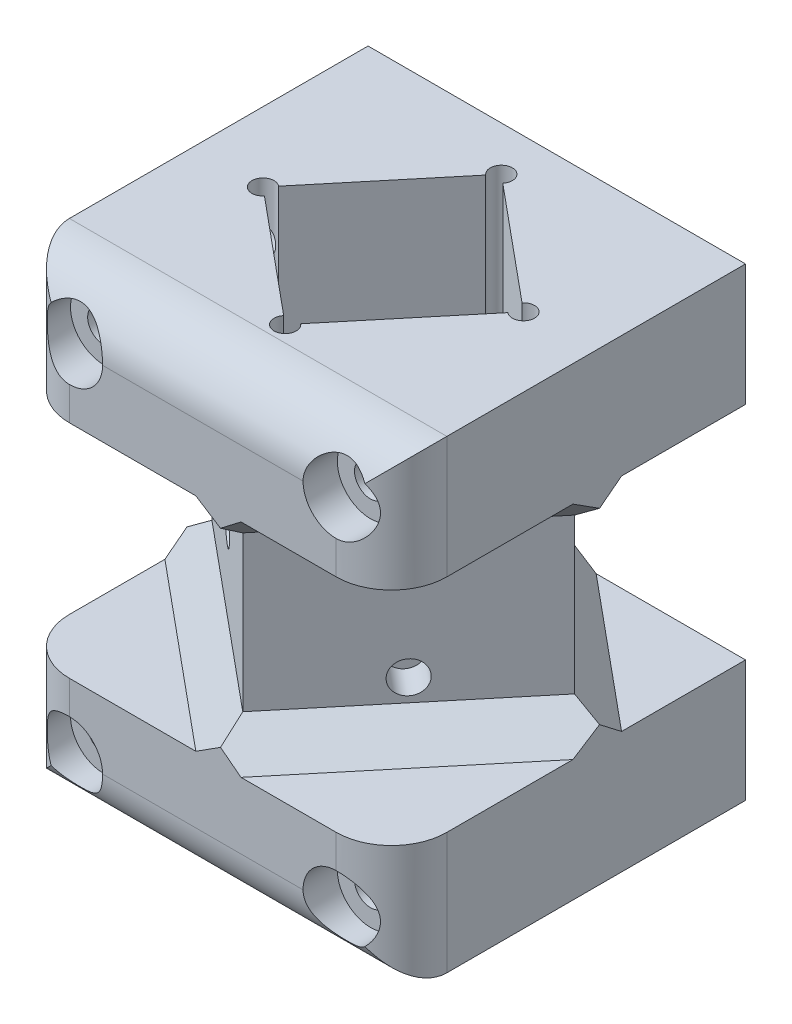
SolidWorks part; units mm, degrees
material "ABS"
ref_plane "前视基准面" through (0, 0, 0) normal (0, 0, 1) x (1, 0, 0)
ref_plane "上视基准面" through (0, 0, 0) normal (0, 1, 0) x (1, 0, 0)
ref_plane "右视基准面" through (0, 0, 0) normal (1, 0, 0) x (0, 0, -1)
other "Configuration Table"
sketch "草图1" plane through (0, 0, 0) normal (0, 0, 1) x (1, 0, 0)
  line L0 (5, 0) -> (5, -42) construction
  line L1 (0, 0) -> (34.1221, 0)
  line L2 (0, 0) -> (0, -42)
  line L3 (0, -42) -> (34.1221, -42)
  line L4 (34.1221, 0) -> (34.1221, -42)
  line L5 (0, -5) -> (34.1221, -5) construction
  line L6 (17.061, 0) -> (17.061, -42) construction
  line L7 (0, -21) -> (34.122, -21) construction
  circle A0 centre (5, -5) radius 1.45
  circle A1 centre (5, -37) radius 1.45
  circle A2 centre (29.1221, -37) radius 1.45
  circle A3 centre (29.1221, -5) radius 1.45
  dimension "D3" = 2.9
  dimension "D1" = 34.1221
  dimension "D2" = 42
  dimension "D4" = 5
  dimension "D5" = 5
extrude "凸台-拉伸1" add sketch "草图1" along normal blind 32
sketch "草图2" plane through (0, 0, 0) normal (0, 1, 0) x (1, 0, 0)
  line L0 (15.686, 0) -> (2.2756, -16.1605) construction
  line L1 (15.686, 0) -> (31.8465, -13.4104) construction
  line L2 (2.2756, -16.1605) -> (18.4361, -29.5709) construction
  line L3 (31.8465, -13.4104) -> (18.4361, -29.5709) construction
  line L4 (34.1221, 0) -> (0, 0) construction
  line L5 (34.1221, -32) -> (0, -32) construction
  line L6 (3.5, 0) -> (6.5, 0) construction
  line L7 (3.5, 0) -> (3.5, -32) construction
  line L8 (3.5, -32) -> (6.5, -32) construction
  line L9 (6.5, 0) -> (6.5, -32) construction
  line L10 (5, 0) -> (5, -32) construction
  line L11 (0, -32) -> (0, 0) construction
  line L12 (16.0788, -4.2244) -> (6.5, -15.7676) construction
  line L13 (6.5, -15.7676) -> (18.0432, -25.3465) construction
  line L14 (27.6221, -13.8033) -> (18.0432, -25.3465) construction
  line L15 (16.0788, -4.2244) -> (27.6221, -13.8033) construction
  line L16 (16.0592, -4.0132) -> (6.2888, -15.7873)
  line L17 (6.2888, -15.7873) -> (18.0629, -25.5577)
  line L18 (27.8333, -13.7836) -> (18.0629, -25.5577)
  line L19 (16.0592, -4.0132) -> (27.8333, -13.7836)
  dimension "D1" = 21
  dimension "D2" = 21
  dimension "D3" = 50.313
  dimension "D4" = 5
  dimension "D5" = 3
  dimension "D6" = 3
  dimension "D7" = 0.15
extrude "切除-拉伸1" cut sketch "草图2" against normal through all
sketch "草图3" plane through (0, 0, 0) normal (0, 1, 0) x (1, 0, 0)
  line L0 (34.1221, -32) -> (16.6153, -32)
  line L18 (15.4911, 0) -> (0, -18.6678)
  line L19 (34.1221, 0) -> (0, 0) construction
  line L20 (0, -32) -> (0, 0) construction
  line L21 (0, -18.6678) -> (0, 0)
  line L22 (2.0644, -16.1801) -> (18.4557, -29.7821)
  line L23 (18.4557, -29.7821) -> (32.0577, -13.3907)
  line L24 (32.0577, -13.3907) -> (15.6663, 0.2112)
  line L25 (15.6663, 0.2112) -> (2.0644, -16.1801)
  line L26 (2.0644, -16.1801) -> (18.4557, -29.7821) construction
  line L27 (18.4557, -29.7821) -> (32.0577, -13.3907) construction
  line L28 (32.0577, -13.3907) -> (15.6663, 0.2112) construction
  line L29 (15.6663, 0.2112) -> (2.0644, -16.1801) construction
  line L30 (0, 0) -> (15.4911, 0)
  line L31 (15.9209, 0) -> (34.1221, -15.1038)
  line L32 (34.1221, -32) -> (34.1221, 0) construction
  line L33 (34.1221, -15.1038) -> (34.1221, 0)
  line L34 (34.1221, 0) -> (15.9209, 0)
  line L35 (21.1285, -32) -> (0, -32) construction
  line L36 (34.1221, -32) -> (0, -32) construction
  line L37 (0, -32) -> (0, -14.4671) construction
  line L38 (0, -14.4671) -> (21.1285, -32) construction
  line L39 (16.6153, -32) -> (34.1221, -32) construction
  line L40 (34.1221, -32) -> (34.1221, -10.903) construction
  line L41 (34.1221, -10.903) -> (16.6153, -32) construction
  line L42 (0, -14.4671) -> (0, -32)
  line L43 (0, -32) -> (21.1285, -32)
  line L44 (21.1285, -32) -> (0, -14.4671)
  line L45 (16.6153, -32) -> (34.1221, -10.903)
  line L46 (34.1221, -10.903) -> (34.1221, -32)
  line M9 (34.1221, -32) -> (34.1221, 0)
  line M10 (34.1221, 0) -> (0, 0)
  line M11 (0, 0) -> (0, -32)
  line M12 (0, -32) -> (34.1221, -32)
  dimension "D1" = 3
extrude "切除-拉伸3" cut sketch "草图3" against normal blind 20 from offset 11 contours L44 L18 M10 M11 | L31 L45 L33 M10 | L45 L31 M9 | L18 L44 L21 region at (33.4339, 0, 13.1325) region at (27.8798, 0, 4.7708) region at (5.302, 0, 5.9068) region at (0.6881, 0, 16.4384) offset against normal yes
extrude "切除-拉伸4" cut sketch "草图3<3>" against normal blind 20 from offset 11 contours L45 L31 M12 M9 | L45 L31 M9 | L44 L18 M12 M11 | L18 L44 L21 | L0 L45 L46 region at (28.4319, 0, 25.0807) region at (33.4339, 0, 13.1325) region at (6.8668, 0, 26.25) region at (0.6881, 0, 16.4384) offset against normal yes
sketch "草图3<3>" plane through (0, 0, 0) normal (0, 1, 0) x (1, 0, 0) same geometry as "草图3"
sketch "草图5" plane through (0, 0, 0) normal (0, 1, 0) x (1, 0, 0)
  circle A0 centre (16.0592, -4.0132) radius 1
  circle A1 centre (27.8333, -13.7836) radius 1
  circle A3 centre (6.2888, -15.7873) radius 1
  circle A4 centre (18.0629, -25.5577) radius 1
  dimension "D1" = 2
extrude "切除-拉伸5" cut sketch "草图5" against normal through all
sketch "草图6" plane through (0, 0, 0) normal (0, 0, -1) x (-1, 0, 0)
  line L1 (-17.9303, -7.5619) -> (-16.0561, -6.4798)
  line L2 (-16.0561, -6.4798) -> (-16.0561, -4.3156)
  line L3 (-16.0561, -4.3156) -> (-17.9303, -3.2335)
  line L4 (-17.9303, -3.2335) -> (-19.8046, -4.3156)
  line L5 (-19.8046, -4.3156) -> (-19.8046, -6.4798)
  line L6 (-19.8046, -6.4798) -> (-17.9303, -7.5619)
  circle A0 centre (-17.9303, -5.3977) radius 1.8743 construction
extrude "切除-拉伸6" cut sketch "草图6" against normal blind 1
sketch "草图4" plane through (11.4825, 0, 9.5285) normal (0.7695, 0, 0.6386) x (0.6386, 0, -0.7695)
  line L0 (-0.4831, 0) -> (-0.4831, -42) construction
  line L1 (6.1669, 0) -> (-7.1331, 0) construction
  line L2 (6.1669, -42) -> (-7.1331, -42) construction
  line L3 (-0.4831, -21) -> (-15.7835, -21) construction
  circle A0 centre (-0.4831, -16) radius 1.45
  circle A1 centre (-0.4831, -26) radius 1.45
  dimension "D1" = 2.9
  dimension "D2" = 5
  dimension "D3" = 5
extrude "切除-拉伸7" cut sketch "草图4" against normal through all and the other way through all
sketch "草图7" plane through (4.5767, 0, -5.5153) normal (-0.6386, 0, 0.7695) x (0.7695, 0, 0.6386)
  line L0 (22.5711, 0) -> (22.5711, -42) construction
  line L1 (29.2211, 0) -> (15.9211, 0) construction
  line L2 (29.2211, -42) -> (15.9211, -42) construction
  circle A0 centre (22.5711, -21) radius 1.45
  dimension "D1" = 2.9
extrude "切除-拉伸8" cut sketch "草图7" against normal through all both and the other way through all
sketch "草图8" plane through (0, 0, 32) normal (0, 0, 1) x (1, 0, 0)
  circle A0 centre (5, -5) radius 3
  circle A1 centre (29.1221, -5) radius 3
  circle A2 centre (5, -37) radius 3
  circle A3 centre (29.1221, -37) radius 3
  dimension "D1" = 6
extrude "切除-拉伸9" cut sketch "草图8" against normal blind 3.1
fillet "圆角1" radius 5 6 edges at (17.061, -42, 32) (17.061, 0, 32) (0, -36.5, 32) (34.1221, -36.5, 32) (0, -5.5, 32) (34.1221, -5.5, 32)
chamfer "倒角1" distance 3 angle 45 8 edges at (8.7777, -31, 8.0901) (23.9893, -31, 6.6954) (25.2567, -31, 21.5864) (8.7777, -11, 8.0901) (25.2567, -11, 21.5864) (23.9893, -11, 6.6954) (10.26, -31, 22.9811) (10.26, -11, 22.9811)
